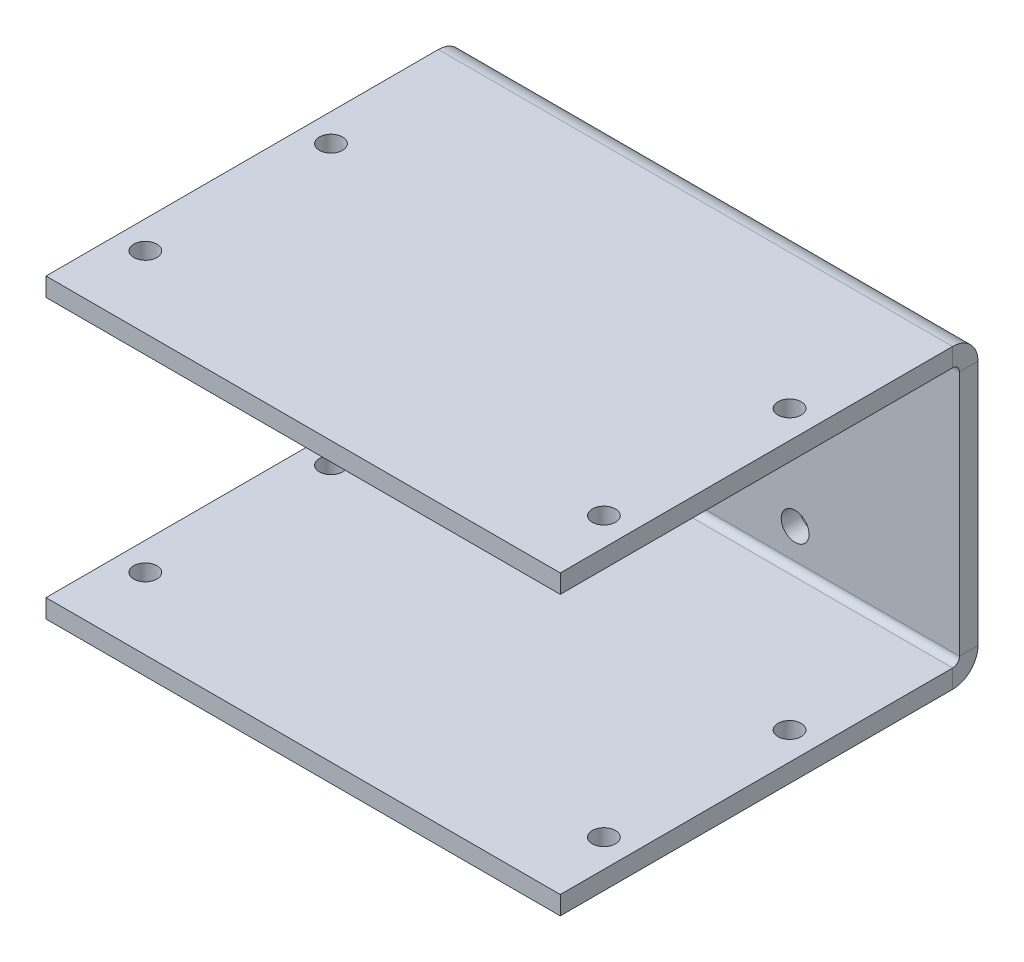
SolidWorks part; units mm, degrees
note: The reader was unsure of these and kept them because the rebuilt part matched: flange length of "Odgięcie krawędzi1".
ref_plane "Płaszczyzna przednia" through (0, 0, 0) normal (0, 0, 1) x (1, 0, 0)
ref_plane "Płaszczyzna górna" through (0, 0, 0) normal (0, 1, 0) x (1, 0, 0)
ref_plane "Płaszczyzna prawa" through (0, 0, 0) normal (1, 0, 0) x (0, 0, -1)
sketch "Szkic1" plane through (0, 0, 0) normal (0, 0, 1) x (1, 0, 0)
  line L1 (-27.7, -14) -> (27.7, -14)
  line L2 (-27.7, -14) -> (-27.7, 14)
  line L3 (-27.7, 14) -> (27.7, 14)
  line L4 (27.7, -14) -> (27.7, 14)
  line L5 (-27.7, -14) -> (27.7, 14) construction
  line L6 (-27.7, 14) -> (27.7, -14) construction
  point P0 (0, 0)
  dimension "D1" = 55.4
  dimension "D2" = 28
base flange "Odgięcie bazowe1" sketch "Szkic1" thickness 2 reverse thickness direction no parameters "D1"=0.7366
hole_wizard "Otwory ustalające Ø3.0mm1" positions "Szkic11" profile "Szkic12" hole size "Ø3.0" standard "Ansi Metric"
sketch "Szkic11" plane through (0, 0, -2) normal (0, 0, -1) x (-1, 0, 0)
  line L0 (0, 14) -> (0, -14) construction
  line L5 (-27.7, 0) -> (27.7, 0) construction
  line L6 (-27.7, -14) -> (-27.7, 14) construction
  line L7 (27.7, 14) -> (27.7, -14) construction
  line L11 (-27.7, 14) -> (27.7, 14) construction
  line L12 (27.7, -14) -> (-27.7, -14) construction
  point P0 (-10, 10)
  point P22 (10, 10)
  point P23 (10, -10)
  point P24 (-10, -10)
  dimension "D1" = 10
  dimension "D2" = 10
sketch "Szkic12" plane through (10, 10, -2) normal (1, 0, 0) x (0, 1, 0)
  line L0 (0, 0) -> (0, 17.9013)
  line L1 (0, 17.9013) -> (1.5, 17)
  line L2 (1.5, 17) -> (1.5, 0)
  line L5 (1.5, 0) -> (0, 0)
  line L10 (0, 17.9013) -> (-1.5, 17) construction
  line L11 (0, -6.35) -> (0, 107.95) construction
  dimension "Średnica otworu" = 3
  dimension "Głębokość otworu" = 17
  dimension "Kąt wiertła" = 118
edge flange "Odgięcie krawędzi1" sketch "Szkic8" flange profiles "Szkic8", "Szkic10" flange angle 90 flange length 45 flange position material outside bend radius 0.7366 thickness 2 relief rectangular parameters "D6"=10, "D8"=1
sketch "Szkic8" plane through (0, 14, 0) normal (0, 1, 0) x (-1, 0, 0)
  line L2 (-27.7, 0) -> (-27.7, 43)
  line L3 (-27.7, 43) -> (27.7, 43)
  line L4 (27.7, 43) -> (27.7, 0)
  line L7 (-27.7, 0) -> (27.7, 0) construction
  line L8 (-27.7, 0) -> (27.7, 0)
sketch "Szkic10" plane through (0, -14, 0) normal (0, -1, 0) x (1, 0, 0)
  line L0 (-27.7, 0) -> (27.7, 0) construction
  line L1 (-27.7, 0) -> (27.7, 0)
  line L2 (-27.7, 0) -> (-27.7, 43)
  line L3 (-27.7, 43) -> (27.7, 43)
  line L4 (27.7, 43) -> (27.7, 0)
bend "Zgięcie krawędziowe1" bend radius 0.7366 bend angle 90 parameters "D5"=1
bend "Zgięcie krawędziowe2" bend radius 0.7366 bend angle 90 parameters "D5"=3
hole_wizard "Otwór gwintowany M3x0.51" positions "Szkic14" profile "Szkic15" tap size "M3x0.5" standard "Ansi Metric" end condition through all
sketch "Szkic14" plane through (0, 16, 0) normal (0, 1, 0) x (1, 0, 0)
  line L0 (-27.7, -43) -> (27.7, -43) construction
  line L1 (-27.7, -0.7366) -> (-27.7, -43) construction
  line L2 (0, 0) -> (0, -43) construction
  point P0 (-24.7, -35.3)
  point P7 (-24.7, -15.3)
  point P14 (24.7, -35.3)
  point P15 (24.7, -15.3)
  dimension "D1" = 7.7
  dimension "D2" = 3
  dimension "D3" = 3
  dimension "D4" = 20
sketch "Szkic15" plane through (-24.7, 16, 35.3) normal (1, 0, 0) x (0, 0, 1)
  line L0 (0, 0) -> (0, 32)
  line L1 (0, 32) -> (1.25, 32)
  line L2 (1.25, 32) -> (1.25, 0)
  line L5 (1.25, 0) -> (0, 0)
  line L11 (0, -6.35) -> (0, 107.95) construction
  dimension "Średnica otworu gwintowanego na wylot" = 2.5
  dimension "Głębokość otworu gwintowanego na wylot" = 32
cosmetic thread "Gwint otworu1"
cosmetic thread "Gwint otworu2"
cosmetic thread "Gwint otworu3"
cosmetic thread "Gwint otworu4"
sketch "Linie zgięcia1" [suppressed] plane through (0, 0, 0) normal (0, 1, 0) x (1, 0, 0)
sketch "Ramka-graniczna1" [suppressed] plane through (0, 0, 0) normal (0, 1, 0) x (1, 0, 0)
sheet metal parameters "Arkusz blachy1" thickness 2 parameters "D1"=0.7366
flat pattern "Rozłożony model1" [suppressed]
sketch "Linie zgięcia2" plane through (0, 0, 0) normal (0, 1, 0) x (1, 0, 0)
sketch3d "Ramka-graniczna2" [suppressed]
  line L0 (22.7, -14, 0) -> (-22.7, -14, 0) construction
  line L1 (22.7, 14, 0) -> (-22.7, 14, 0) construction
  line L2 (22.7, -14, 0) -> (22.7, 14, 0) construction
  line L3 (-22.7, -14, 0) -> (-22.7, 14, 0) construction
sheet metal parameters "Arkusz blachy2" thickness 2 parameters "D1"=0.7366
flat pattern "Rozłożony model1"
sketch "Linie zgięcia2" plane through (0, 0, 0) normal (0, 0, 1) x (1, 0, 0)
  line L0 (27.7, 14.6273) -> (-27.7, 14.6273) construction
  line L1 (27.7, 14.6273) -> (-27.7, 14.6273) construction
  line L2 (-27.7, -14.6273) -> (27.7, -14.6273) construction
  line L3 (-27.7, -14.6273) -> (27.7, -14.6273) construction
sketch3d "Ramka-graniczna2" [suppressed]
  line L0 (27.7, 58.2546, 0) -> (27.7, -58.2546, 0) construction
  line L1 (-27.7, 58.2546, 0) -> (-27.7, -58.2546, 0) construction
  line L2 (27.7, 58.2546, 0) -> (-27.7, 58.2546, 0) construction
  line L3 (27.7, -58.2546, 0) -> (-27.7, -58.2546, 0) construction
bend of the flat pattern "Rozłożone-<Zgięcie krawędziowe1>1"
bend of the flat pattern "Rozłożone-<Zgięcie krawędziowe2>1"
sheet metal parameters "Arkusz blachy3" thickness 2 parameters "D1"=0.7366
flat pattern "Rozłożony model1"
sketch "Linie zgięcia2" plane through (0, 0, 0) normal (0, 0, 1) x (1, 0, 0)
  line L0 (22.7, 14.6273) -> (-22.7, 14.6273) construction
  line L1 (22.7, 14.6273) -> (-22.7, 14.6273) construction
  line L2 (-22.7, -14.6273) -> (22.7, -14.6273) construction
  line L3 (-22.7, -14.6273) -> (22.7, -14.6273) construction
sketch3d "Ramka-graniczna2" [suppressed]
  line L0 (22.7, 58.2546, 0) -> (22.7, -58.2546, 0) construction
  line L1 (-22.7, 58.2546, 0) -> (-22.7, -58.2546, 0) construction
  line L2 (22.7, 58.2546, 0) -> (-22.7, 58.2546, 0) construction
  line L3 (22.7, -58.2546, 0) -> (-22.7, -58.2546, 0) construction
sheet metal parameters "Arkusz blachy4" thickness 2 parameters "D1"=0.7366
flat pattern "Rozłożony model1"
sketch "Linie zgięcia2" plane through (0, 0, 0) normal (0, 0, 1) x (1, 0, 0)
  line L0 (27.7, 14.6273) -> (-27.7, 14.6273) construction
  line L1 (27.7, 14.6273) -> (-27.7, 14.6273) construction
  line L2 (-27.7, -14.6273) -> (27.7, -14.6273) construction
  line L3 (-27.7, -14.6273) -> (27.7, -14.6273) construction
sketch3d "Ramka-graniczna2" [suppressed]
  line L0 (27.7, 58.2546, 0) -> (27.7, -58.2546, 0) construction
  line L1 (-27.7, 58.2546, 0) -> (-27.7, -58.2546, 0) construction
  line L2 (27.7, 58.2546, 0) -> (-27.7, 58.2546, 0) construction
  line L3 (27.7, -58.2546, 0) -> (-27.7, -58.2546, 0) construction
bend of the flat pattern "Rozłożone-<Zgięcie krawędziowe1>1"
bend of the flat pattern "Rozłożone-<Zgięcie krawędziowe2>1"
